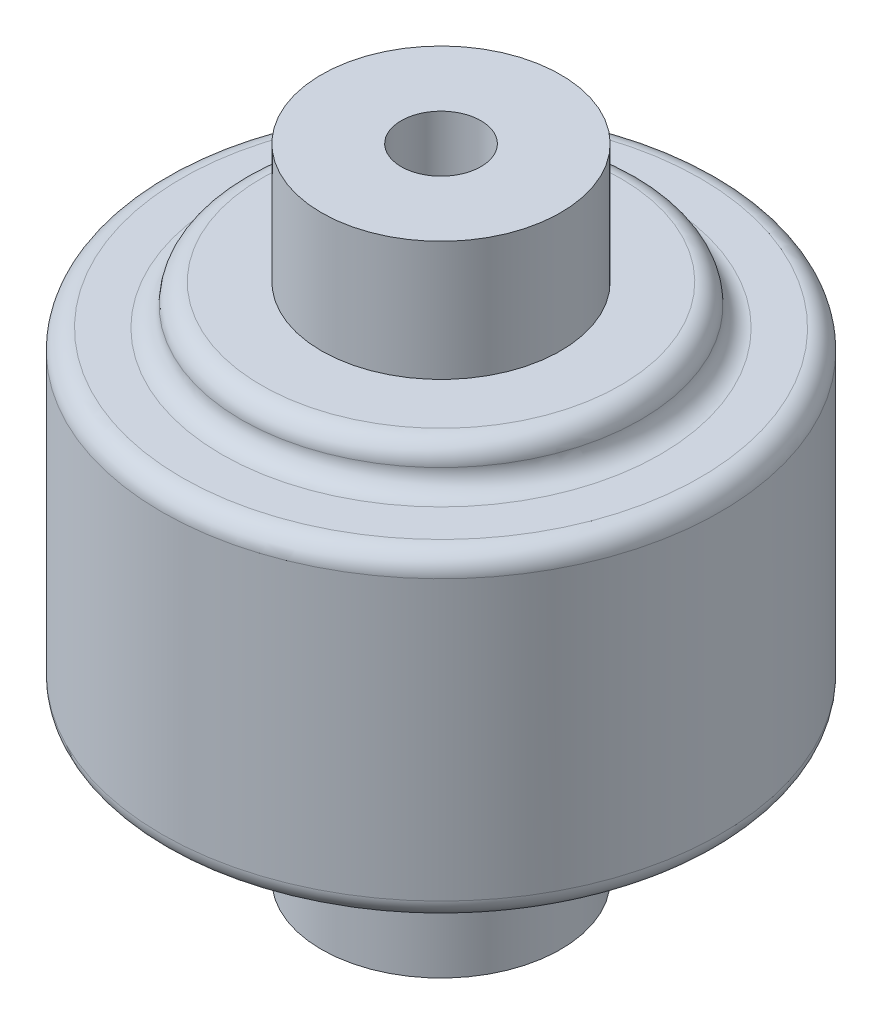
SolidWorks part; units mm, degrees
material "Silicon Rubber"
ref_plane "Front Plane" through (0, 0, 0) normal (0, 0, 1) x (1, 0, 0)
ref_plane "Top Plane" through (0, 0, 0) normal (0, 1, 0) x (1, 0, 0)
ref_plane "Right Plane" through (0, 0, 0) normal (1, 0, 0) x (0, 0, -1)
sketch "Sketch2" plane through (0, 0, 0) normal (0, 0, 1) x (1, 0, 0)
  line L0 (0, -4) -> (0, 4) construction
  line L1 (0, 0) -> (3.5, 0) construction
  line L2 (3.5, -2) -> (3.5, 2)
  line L3 (3.5, 2) -> (2.5, 2)
  line L4 (2.5, 2) -> (2.5, 2.5)
  line L5 (2.5, 2.5) -> (1.5, 2.5)
  line L6 (1.5, 2.5) -> (1.5, 4)
  line L7 (1.5, 4) -> (0, 4)
  line L8 (2.5, -2) -> (2.5, -2.5)
  line L9 (3.5, -2) -> (2.5, -2)
  line L10 (2.5, -2.5) -> (1.5, -2.5)
  line L11 (1.5, -2.5) -> (1.5, -4)
  line L12 (1.5, -4) -> (0, -4)
  line L13 (0, 4) -> (0, -4)
  dimension "D1" = 7
  dimension "D2" = 5
  dimension "D3" = 3
  dimension "D4" = 1.5
  dimension "D5" = 0.5
  dimension "D6" = 2
revolve "Revolve1" add sketch "Sketch2" angle 360 about L13
fillet "Fillet1" radius 0.25 6 edges at (0, 2.5, 2.5) (0, 2, 2.5) (0, 2, 3.5) (0, -2.5, 2.5) (0, -2, 2.5) (0, -2, 3.5)
sketch "Sketch3" plane through (0, 4, 0) normal (0, 1, 0) x (1, 0, 0)
  circle A0 centre (0, 0) radius 0.5
  dimension "D1" = 1
extrude "Cut-Extrude1" cut sketch "Sketch3" against normal blind 2.5 contours A0
mirror "Mirror1" about plane through (0, 0, 0) normal (0, 1, 0) of "Cut-Extrude1"
